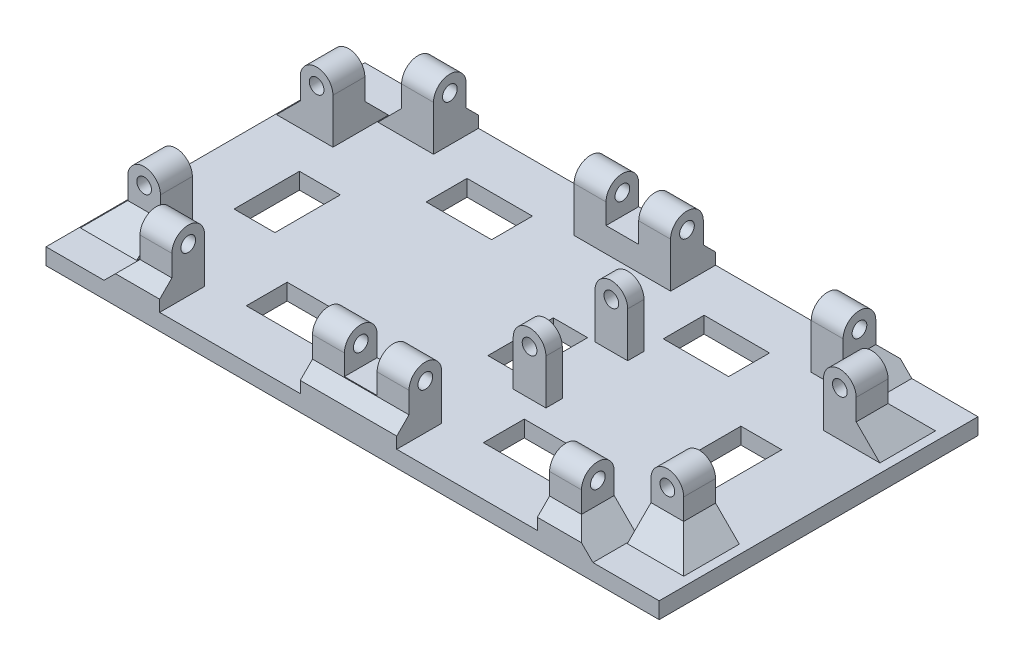
SolidWorks part; units mm, degrees
ref_plane "Front Plane" through (0, 0, 0) normal (0, 0, 1) x (1, 0, 0)
ref_plane "Top Plane" through (0, 0, 0) normal (0, 1, 0) x (1, 0, 0)
ref_plane "Right Plane" through (0, 0, 0) normal (1, 0, 0) x (0, 0, -1)
sketch "Sketch2" plane through (0, 0, 0) normal (0, 1, 0) x (1, 0, 0)
  line L1 (-37.5, -19.5) -> (37.5, -19.5)
  line L2 (-37.5, -19.5) -> (-37.5, 19.5)
  line L3 (-37.5, 19.5) -> (37.5, 19.5)
  line L4 (37.5, -19.5) -> (37.5, 19.5)
  line L5 (0, 19.5) -> (0, -19.5) construction
  line L6 (-37.5, 0) -> (37.5, 0) construction
  point P0 (0, 0)
  dimension "D1" = 75
  dimension "D2" = 39
extrude "Boss-Extrude1" add sketch "Sketch2" along normal blind 2
sketch "Sketch3" plane through (-37.5, 0, 0) normal (-1, 0, 0) x (0, 0, 1)
  line L0 (-19.5, 2) -> (19.5, 2) construction
  line L1 (-18, 2) -> (-14, 2)
  line L2 (-18, 2) -> (-18, 7.5)
  line L4 (-14, 2) -> (-14, 7.5)
  line L5 (18, 2) -> (18, 7.5)
  line L6 (14, 2) -> (18, 2)
  line L7 (14, 2) -> (14, 7.5)
  line L8 (0, 0) -> (0, 2) construction
  line L9 (-19.5, 0) -> (19.5, 0) construction
  arc A0 (-14, 7.5) -> (-18, 7.5) centre (-16, 7.5) ccw
  circle A1 centre (-16, 7.5) radius 0.9
  arc A2 (18, 7.5) -> (14, 7.5) centre (16, 7.5) ccw
  circle A3 centre (16, 7.5) radius 0.9
  dimension "D5" = 1.8
  dimension "D10" = 1.8
  dimension "D1" = 4
  dimension "D2" = 5.5
  dimension "D6" = 28
  dimension "D7" = 4
  dimension "D9" = 5.5
extrude "Boss-Extrude2" add sketch "Sketch3" against normal blind 25 from offset 10 offset against normal yes
extrude "Boss-Extrude4" add sketch "Sketch3<2>" against normal blind 25 from offset 39 offset against normal yes
sketch "Sketch3<2>" plane through (-37.5, 0, 0) normal (-1, 0, 0) x (0, 0, 1) same geometry as "Sketch3"
sketch "Sketch7" plane through (0, 0, 0) normal (0, 0, 1) x (1, 0, 0)
  line L1 (-34.5, 2) -> (-30.5, 2)
  line L2 (-34.5, 2) -> (-34.5, 7.5)
  line L4 (-30.5, 2) -> (-30.5, 7.5)
  line L5 (33.5, 2) -> (33.5, 7.5)
  line L6 (29.5, 2) -> (33.5, 2)
  line L7 (29.5, 2) -> (29.5, 7.5)
  line L8 (-27.5, 2) -> (-27.5, 7.5) construction
  line L9 (-37.5, 2) -> (37.5, 2) construction
  line L10 (26.5, 2) -> (26.5, 7.5) construction
  arc A0 (-30.5, 7.5) -> (-34.5, 7.5) centre (-32.5, 7.5) ccw
  circle A1 centre (-32.5, 7.5) radius 0.9
  arc A2 (33.5, 7.5) -> (29.5, 7.5) centre (31.5, 7.5) ccw
  circle A3 centre (31.5, 7.5) radius 0.9
  dimension "D5" = 1.8
  dimension "D10" = 1.8
  dimension "D1" = 4
  dimension "D2" = 5.5
  dimension "D7" = 4
  dimension "D9" = 5.5
  dimension "D3" = 3
  dimension "D6" = 3
extrude "Boss-Extrude5" add sketch "Sketch7" along normal blind 12.5 and the other way blind 12.5
sketch "Sketch4" plane through (0, 0, -18) normal (0, 0, -1) x (-1, 0, 0)
  line L0 (-37.5, 2) -> (37.5, 2) construction
  line L1 (6.4, 2) -> (23.6, 2)
  line L2 (6.4, 2) -> (6.4, 9.5)
  line L3 (6.4, 9.5) -> (23.6, 9.5)
  line L4 (23.6, 2) -> (23.6, 9.5)
  line L5 (15, 9.5) -> (15, 2) construction
  line L6 (6.4, 5.75) -> (23.6, 5.75) construction
  line L7 (27.5, 9.5) -> (2.5, 9.5) construction
  line L10 (27.5, 7.5) -> (27.5, 2) construction
  line L11 (2.5, 7.5) -> (2.5, 2) construction
  line L12 (-1.5, 9.5) -> (-26.5, 9.5) construction
  line L13 (-22.6, 9.5) -> (-5.4, 9.5)
  line L14 (-22.6, 9.5) -> (-22.6, 2)
  line L15 (-22.6, 2) -> (-5.4, 2)
  line L16 (-5.4, 9.5) -> (-5.4, 2)
  line L17 (-14, 2) -> (-14, 9.5) construction
  line L18 (-22.6, 5.75) -> (-5.4, 5.75) construction
  line L19 (-1.5, 7.5) -> (-1.5, 2) construction
  line L20 (-26.5, 7.5) -> (-26.5, 2) construction
  point P264 (15, 5.75)
  point P272 (-14, 5.75)
  dimension "D1" = 17.2
extrude "Cut-Extrude1" cut sketch "Sketch4" against normal through all
sketch "Sketch5" plane through (0, 2, 0) normal (0, 1, 0) x (1, 0, 0)
  line L0 (-27.5, 16) -> (-2.5, 16) construction
  line L3 (-27.5, 18) -> (-27.5, 14) construction
  line L4 (-19, 8.5) -> (-11, 8.5)
  line L5 (-19, 8.5) -> (-19, 13.5)
  line L6 (-19, 13.5) -> (-11, 13.5)
  line L7 (-11, 8.5) -> (-11, 13.5)
  line L8 (-15, 13.5) -> (-15, 8.5) construction
  line L9 (-19, 11) -> (-11, 11) construction
  line L10 (-2.5, 14) -> (-2.5, 18) construction
  line L11 (1.5, 16) -> (26.5, 16) construction
  line L12 (1.5, 18) -> (1.5, 14) construction
  line L13 (26.5, 14) -> (26.5, 18) construction
  line L14 (-27.5, -16) -> (-2.5, -16) construction
  line L15 (10, 13.5) -> (18, 13.5)
  line L16 (10, 13.5) -> (10, 8.5)
  line L17 (10, 8.5) -> (18, 8.5)
  line L18 (18, 13.5) -> (18, 8.5)
  line L19 (14, 8.5) -> (14, 13.5) construction
  line L20 (10, 11) -> (18, 11) construction
  line L21 (-27.5, -14) -> (-27.5, -18) construction
  line L22 (-2.5, -18) -> (-2.5, -14) construction
  line L23 (1.5, -16) -> (26.5, -16) construction
  line L24 (1.5, -14) -> (1.5, -18) construction
  line L25 (26.5, -18) -> (26.5, -14) construction
  line L26 (-34.5, -12.5) -> (-30.5, -12.5) construction
  line L27 (-19, -8.5) -> (-11, -8.5)
  line L28 (-19, -8.5) -> (-19, -13.5)
  line L29 (-19, -13.5) -> (-11, -13.5)
  line L30 (-11, -8.5) -> (-11, -13.5)
  line L31 (-15, -13.5) -> (-15, -8.5) construction
  line L32 (-19, -11) -> (-11, -11) construction
  line L33 (10, -8.5) -> (18, -8.5)
  line L34 (10, -8.5) -> (10, -13.5)
  line L35 (10, -13.5) -> (18, -13.5)
  line L36 (18, -8.5) -> (18, -13.5)
  line L37 (14, -13.5) -> (14, -8.5) construction
  line L38 (10, -11) -> (18, -11) construction
  line L39 (24, 4) -> (29, 4)
  line L40 (24, 4) -> (24, -4)
  line L41 (24, -4) -> (29, -4)
  line L42 (29, 4) -> (29, -4)
  line L43 (26.5, -4) -> (26.5, 4) construction
  line L44 (24, 0) -> (29, 0) construction
  line L45 (-30, 4) -> (-25, 4)
  line L46 (-30, 4) -> (-30, -4)
  line L47 (-30, -4) -> (-25, -4)
  line L48 (-25, 4) -> (-25, -4)
  line L49 (-27.5, -4) -> (-27.5, 4) construction
  line L50 (-30, 0) -> (-25, 0) construction
  line L51 (29.5, -12.5) -> (33.5, -12.5) construction
  point P6 (-15, 11)
  point P10 (-15, 16)
  point P21 (14, 16)
  point P42 (-15, -16)
  point P43 (14, -16)
  point P54 (-32.5, -12.5)
  point P57 (31.5, -12.5)
  point P172 (-15, -11)
  point P187 (26.5, 0)
  point P188 (-27.5, 0)
  point P217 (14, -11)
  dimension "D1" = 8
  dimension "D3" = 5
  dimension "D2" = 5
  dimension "D4" = 5
  dimension "D5" = 8
  dimension "D6" = 5
  dimension "D7" = 5
  dimension "D8" = 5
extrude "Cut-Extrude2" cut sketch "Sketch5" against normal up to next
sketch "Sketch8" plane through (-34.5, 0, 0) normal (-1, 0, 0) x (0, 0, 1)
  line L0 (12.5, 9.5) -> (-12.5, 9.5) construction
  line L1 (8.6, 9.5) -> (-8.6, 9.5)
  line L2 (8.6, 9.5) -> (8.6, 2)
  line L3 (8.6, 2) -> (-8.6, 2)
  line L4 (-8.6, 9.5) -> (-8.6, 2)
  line L5 (0, 2) -> (0, 9.5) construction
  line L6 (8.6, 5.75) -> (-8.6, 5.75) construction
  line L7 (-19.5, 2) -> (19.5, 2) construction
  point P236 (0, 5.75)
  dimension "D1" = 17.2
extrude "Cut-Extrude3" cut sketch "Sketch8" against normal through all
sketch "Sketch9" plane through (0, 0, 0) normal (0, 0, 1) x (1, 0, 0)
  line L11 (10.15, 2) -> (10.15, 7.5)
  line L12 (6.15, 2) -> (10.15, 2)
  line L13 (6.15, 2) -> (6.15, 7.5)
  line L17 (5.4, 7.5) -> (5.4, 2) construction
  arc A4 (10.15, 7.5) -> (6.15, 7.5) centre (8.15, 7.5) ccw
  circle A5 centre (8.15, 7.5) radius 0.9
  dimension "D3" = 1.8
  dimension "D1" = 5.5
  dimension "D4" = 4
  dimension "D5" = 2.75
  dimension "D6" = 2
extrude "Boss-Extrude6" add sketch "Sketch9" along normal blind 6 and the other way blind 6 contours L11 A4 L13 L12 A5 region at (8.15, 5.3566, 0)
sketch "Sketch10" plane through (10.15, 0, 0) normal (1, 0, 0) x (0, 0, -1)
  line L0 (6, 9.5) -> (-6, 9.5) construction
  line L1 (-19.5, 2) -> (19.5, 2) construction
  line L2 (-4, 9.5) -> (4, 9.5)
  line L3 (-4, 9.5) -> (-4, 2)
  line L4 (-4, 2) -> (4, 2)
  line L5 (4, 9.5) -> (4, 2)
  line L6 (0, 2) -> (0, 9.5) construction
  line L7 (-4, 5.75) -> (4, 5.75) construction
  line L9 (-6, 2) -> (-6, 7.5) construction
  line L10 (6, 2) -> (6, 7.5) construction
  point P216 (0, 5.75)
  dimension "D1" = 8
extrude "Cut-Extrude4" cut sketch "Sketch10" against normal up to next
sketch "Sketch11" plane through (0, 2, 0) normal (0, 1, 0) x (1, 0, 0)
  line L0 (8.15, -6) -> (8.15, 6) construction
  line L1 (5.25, -4) -> (1.05, -4)
  line L2 (5.25, -4) -> (5.25, 4)
  line L3 (5.25, 4) -> (1.05, 4)
  line L4 (1.05, -4) -> (1.05, 4)
  line L5 (3.15, 4) -> (3.15, -4) construction
  line L6 (5.25, 0) -> (1.05, 0) construction
  line L7 (6.15, -6) -> (10.15, -6) construction
  line L8 (10.15, 6) -> (6.15, 6) construction
  point P10 (8.15, 0)
  point P108 (3.15, 0)
  dimension "D1" = 8
  dimension "D2" = 4.2
  dimension "D3" = 5
extrude "Cut-Extrude5" cut sketch "Sketch11" against normal up to next
sketch "Sketch12" plane through (0, 2, 0) normal (0, 1, 0) x (1, 0, 0)
  line L5 (-2.5, -18) -> (-2.5, -14) construction
  line L6 (-2.5, -14) -> (1.5, -14)
  line L10 (37.5, 0) -> (-37.5, 0) construction
  line L11 (37.5, -19.5) -> (37.5, 19.5) construction
  line L12 (-37.5, 19.5) -> (-37.5, -19.5) construction
  line L19 (-2.5, -14) -> (-2.5, -18)
  line L20 (-2.5, -18) -> (1.5, -18)
  line L21 (1.5, -14) -> (1.5, -18)
  line L22 (-0.5, -18) -> (-0.5, -14) construction
  line L23 (-2.5, -16) -> (1.5, -16) construction
  line L25 (1.5, -14) -> (1.5, -18) construction
  line L26 (-2.5, -14) -> (-6.4, -14) construction
  line L27 (-2.5, 16) -> (1.5, 16) construction
  line L28 (-0.5, 18) -> (-0.5, 14) construction
  line L29 (1.5, 14) -> (1.5, 18)
  line L30 (-2.5, 18) -> (1.5, 18)
  line L31 (-2.5, 14) -> (-2.5, 18)
  line L32 (-2.5, 14) -> (1.5, 14)
  line L33 (-2.5, -18) -> (-6.4, -18) construction
  point P26 (-0.5, 16)
  point P138 (-0.5, -16)
extrude "Boss-Extrude7" add sketch "Sketch12" along normal blind 3
chamfer "Chamfer1" distance 2.9 angle 45 18 edges at (-34.5, 2, -10.55) (-32.5, 2, -12.5) (-27.5, 2, -16) (-25.55, 2, -18) (-0.5, 2, -18) (24.55, 2, -18) (26.5, 2, -16) (31.5, 2, -12.5) (33.5, 2, -10.55) (33.5, 2, 10.55) (31.5, 2, 12.5) (26.5, 2, 16) (24.55, 2, 18) (-0.5, 2, 18) (-34.5, 2, 10.55) (-32.5, 2, 12.5) (-25.55, 2, 18) (-27.5, 2, 16)
equation "\"D5@Sketch5\"=\"D1@Sketch5\""
equation "\"NON-CLEARANCE HOLE\"= 1.8mm"
equation "\"D5@Sketch3\"=\"NON-CLEARANCE HOLE\""
equation "\"D10@Sketch3\"=\"NON-CLEARANCE HOLE\""
equation "\"D5@Sketch7\"=\"NON-CLEARANCE HOLE\""
equation "\"D10@Sketch7\"=\"NON-CLEARANCE HOLE\""
equation "\"D3@Sketch9\"=\"NON-CLEARANCE HOLE\""
equation "\"D4@Sketch5\"=\"D3@Sketch5\""
